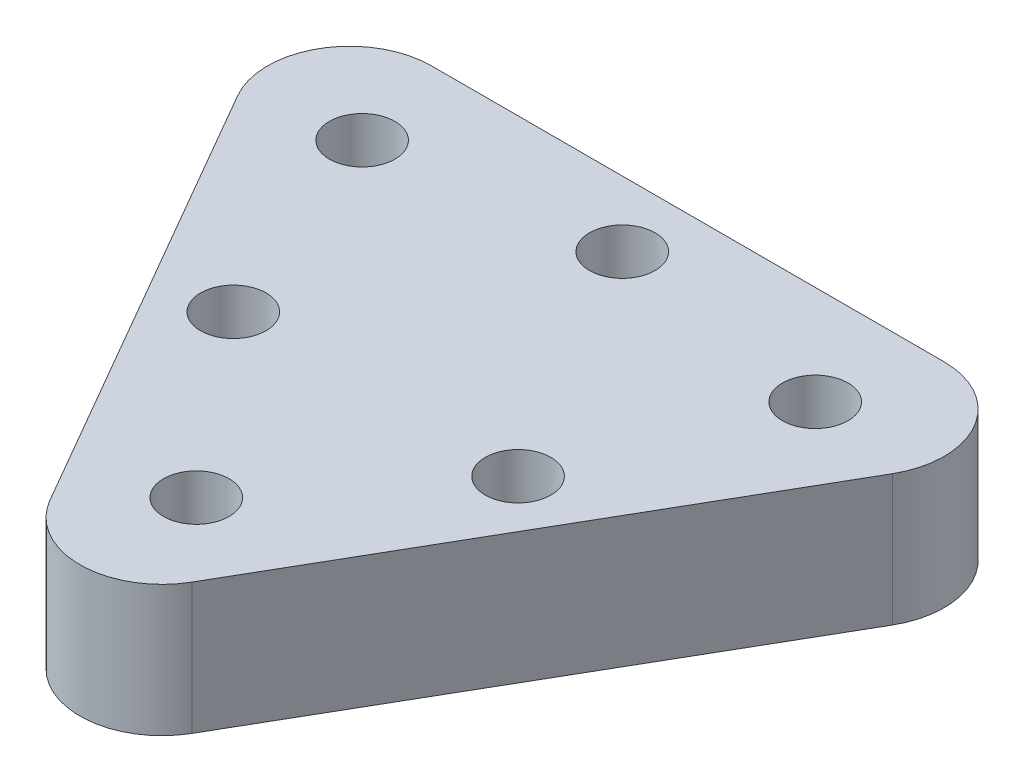
SolidWorks part; units mm, degrees
material "Chrome Stainless Steel"
ref_plane "Front Plane" through (0, 0, 0) normal (0, 0, 1) x (1, 0, 0)
ref_plane "Top Plane" through (0, 0, 0) normal (0, 1, 0) x (1, 0, 0)
ref_plane "Right Plane" through (0, 0, 0) normal (1, 0, 0) x (0, 0, -1)
sketch "Sketch1" plane through (0, 0, 0) normal (0, 1, 0) x (1, 0, 0)
  line L0 (-5.186, 3.3162) -> (2.6377, -10.235)
  line L1 (6.9679, -10.235) -> (14.7916, 3.3162)
  line L2 (12.6266, 7.0662) -> (-3.021, 7.0662)
  line L3 (-1.2742, -3.4594) -> (15.2246, 6.0662) construction
  line L4 (4.8028, 7.0662) -> (4.8028, -11.985) construction
  line L5 (10.8797, -3.4594) -> (-5.6191, 6.0662) construction
  circle A0 centre (-2.1106, 4.0406) radius 2.3812
  circle A1 centre (-2.1106, 4.0406) radius 1
  circle A2 centre (11.7162, 4.0406) radius 1
  circle A3 centre (4.8028, -7.9338) radius 1
  circle A4 centre (4.8028, -7.9338) radius 2.3812
  circle A5 centre (11.7162, 4.0406) radius 2.3812
  arc A15 (-5.186, 3.3162) -> (-3.021, 7.0662) centre (-3.021, 4.5662) cw
  arc A16 (14.7916, 3.3162) -> (12.6266, 7.0662) centre (12.6266, 4.5662) ccw
  arc A17 (6.9679, -10.235) -> (2.6377, -10.235) centre (4.8028, -8.985) cw
  point P9 (-7.3511, 7.0662)
  point P12 (4.8028, -13.985)
  point P22 (4.8028, 0.0491)
  dimension "D1" = 4.7625
  dimension "D5" = 2
  dimension "D9" = 4.7625
  dimension "D10" = 4.7625
  dimension "D12" = 2.5
  dimension "D2" = 300
  dimension "D3" = 60
  dimension "D4" = 24.3078
  dimension "D6" = 15
  dimension "D7" = 15
  dimension "D8" = 15
extrude "Extrude1" add sketch "Sketch1" along normal blind 4 contours A0 | A17 L1 A16 L2 A15 L0 A5 A4 A0 | A5 | A4 region at (4.8028, 0, -0.0491) region at (-4.4245, 0, -4.0406) region at (2.4889, 0, 7.9338) region at (9.4023, 0, -4.0406)
extrude "Extrude4" cut sketch "Sketch1<3>" along normal blind 2 contours A4 | A5 | A0 region at (2.4889, 0, 7.9338) region at (9.4023, 0, -4.0406)
sketch "Sketch1<3>" plane through (0, 0, 0) normal (0, 1, 0) x (1, 0, 0) same geometry as "Sketch1"
sketch "Sketch2" plane through (0, 0, 0) normal (0, -1, 0) x (1, 0, 0)
  line L0 (4.8028, -8.1773) -> (4.8028, 12.2506) construction
  line L1 (-3.5817, 4.7917) -> (16.7524, -6.9482) construction
  line L2 (12.7038, 4.5125) -> (-7.1468, -6.9482) construction
hole_wizard "M2x0.4 Tapped Hole1" positions "3DSketch1" profile "Sketch3" tap size "M2x0.4" standard "Ansi Metric"
sketch3d "3DSketch1"
  line L0 (4.8028, 0, -8.1773) -> (4.8028, 0, 12.2506) construction
  line L1 (12.7038, 0, 4.5125) -> (-7.1468, 0, -6.9482) construction
  point P0 (4.8028, 0, -0.0491)
sketch "Sketch3" plane through (4.8028, 0, -0.0491) normal (1, 0, 0) x (0, 0, -1)
  line L0 (0, 0) -> (0, 3.4807)
  line L1 (0, 3.4807) -> (0.8, 3)
  line L2 (0.8, 3) -> (0.8, 0)
  line L5 (0.8, 0) -> (0, 0)
  line L10 (0, 3.4807) -> (-0.8, 3) construction
  line L11 (0, -6.35) -> (0, 107.95) construction
  dimension "Tap Drill Dia." = 1.6
  dimension "Tap Drill Depth" = 3
  dimension "Drill Angle" = 118
hole_wizard "Ø2.0 (2) Diameter Hole1" positions "3DSketch2" profile "Sketch4" hole size "Ø2.0" standard "Ansi Metric"
sketch3d "3DSketch2"
  line L0 (-3.5817, 0, 4.7917) -> (16.7524, 0, -6.9482) construction
  line L1 (12.7038, 0, 4.5125) -> (-7.1468, 0, -6.9482) construction
  line L2 (4.8028, 0, -8.1773) -> (4.8028, 0, 12.2506) construction
  line L3 (-5.186, 0, -3.3162) -> (2.6377, 0, 10.235) construction
  line L4 (6.9679, 0, 10.235) -> (14.7916, 0, -3.3162) construction
  line L5 (12.6266, 0, -7.0662) -> (-3.021, 0, -7.0662) construction
  point P0 (0.4579, 0, 2.4594)
  point P4 (9.1477, 0, 2.4594)
  point P8 (4.8028, 0, -5.0662)
  dimension "D1" = 2
  dimension "D2" = 2
  dimension "D3" = 2
sketch "Sketch4" plane through (0.4579, 0, 2.4594) normal (1, 0, 0) x (0, 0, -1)
  line L0 (0, 0) -> (0, 10.6009)
  line L1 (0, 10.6009) -> (1, 10)
  line L2 (1, 10) -> (1, 0)
  line L5 (1, 0) -> (0, 0)
  line L10 (0, 10.6009) -> (-1, 10) construction
  line L11 (0, -6.35) -> (0, 107.95) construction
  dimension "Hole Dia." = 2
  dimension "Hole Depth" = 10
  dimension "Drill Angle" = 118
